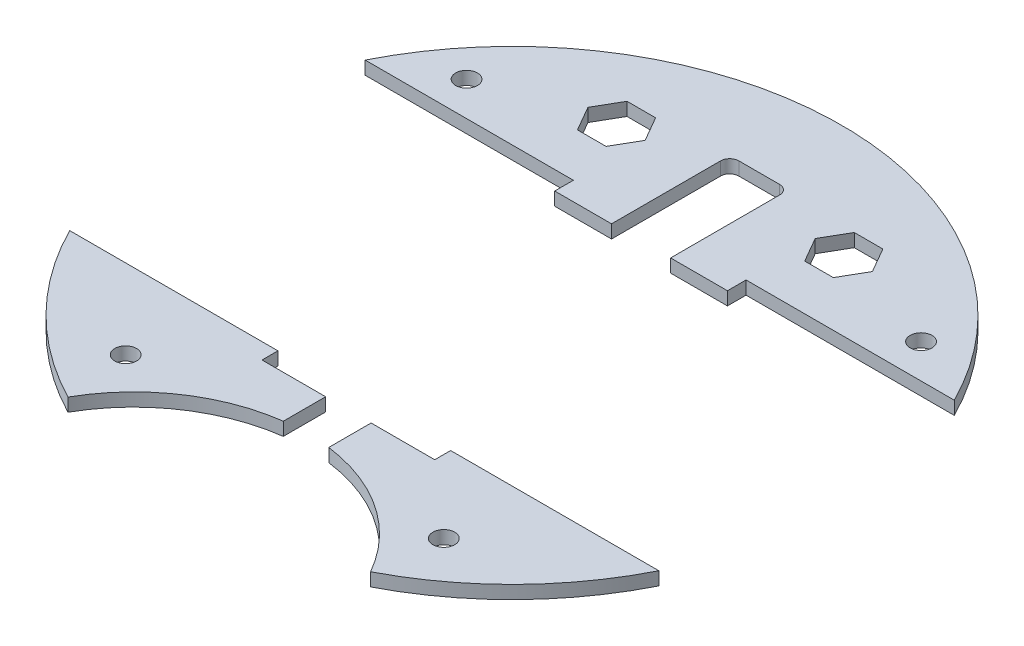
SolidWorks part; units mm, degrees
material "Acrylic (Medium-high impact)"
ref_plane "Front Plane" through (0, 0, 0) normal (0, 0, 1) x (1, 0, 0)
ref_plane "Top Plane" through (0, 0, 0) normal (0, 1, 0) x (1, 0, 0)
ref_plane "Right Plane" through (0, 0, 0) normal (1, 0, 0) x (0, 0, -1)
sketch "Sketch1" plane through (0, 0, 0) normal (0, 1, 0) x (1, 0, 0)
  line L0 (0, -83.2398) -> (-33.2911, -64.4046) construction
  line L1 (0, -83.2398) -> (0, 0) construction
  arc A0 (33.2911, -64.4046) -> (-33.2911, -64.4046) centre (0, 0) ccw
  arc A1 (33.2911, -64.4046) -> (-33.2911, -64.4046) centre (0, -83.2398) ccw
  dimension "D1" = 145
  dimension "D2" = 76.5
  dimension "D3" = 60.5
extrude "Boss-Extrude1" add sketch "Sketch1" along normal blind 2.9
sketch "solenoid placement" plane through (0, 2.9, 0) normal (0, 1, 0) x (1, 0, 0)
  line L4 (-19, -36) -> (19, -36)
  line L5 (-19, 28.4) -> (-19, -36)
  line L6 (19, 28.4) -> (-19, 28.4)
  line L7 (19, -36) -> (19, 28.4)
  line L8 (-19, -36) -> (19, -36)
  line L9 (-19, 28.4) -> (-19, -36)
  line L10 (19, 28.4) -> (-19, 28.4)
  line L11 (19, -36) -> (19, 28.4)
  dimension "D1" = 0
extrude "Cut-Extrude1" cut sketch "solenoid placement" against normal through all
sketch "Sketch4" plane through (0, 2.9, 0) normal (0, 1, 0) x (1, 0, 0)
  line L6 (-6.5, 28.1) -> (6.5, 28.1)
  line L7 (6.5, 28.1) -> (6.5, 52.4)
  line L8 (4.5, 54.4) -> (-4.5, 54.4)
  line L9 (-6.5, 52.4) -> (-6.5, 28.1)
  line L10 (-6.5, 28.1) -> (6.5, 28.1)
  line L11 (6.5, 28.1) -> (6.5, 52.4)
  line L12 (4.5, 54.4) -> (-4.5, 54.4)
  line L13 (-6.5, 52.4) -> (-6.5, 28.1)
  arc A4 (6.5, 52.4) -> (4.5, 54.4) centre (4.5, 52.4) ccw
  arc A5 (6.5, 52.4) -> (4.5, 54.4) centre (4.5, 52.4) ccw
  arc A6 (-4.5, 54.4) -> (-6.5, 52.4) centre (-4.5, 52.4) ccw
  arc A7 (-4.5, 54.4) -> (-6.5, 52.4) centre (-4.5, 52.4) ccw
  dimension "D1" = 0
extrude "Cut-Extrude4" cut sketch "Sketch4" against normal through all
sketch "Sketch5" plane through (0, 2.9, 0) normal (0, 1, 0) x (1, 0, 0)
  line L0 (0, 0) -> (0, 72.5) construction
  line L1 (-18.7069, 48) -> (-21.8534, 53.45)
  line L2 (-21.8534, 53.45) -> (-28.1466, 53.45)
  line L3 (-28.1466, 53.45) -> (-31.2931, 48)
  line L4 (-31.2931, 48) -> (-28.1466, 42.55)
  line L5 (-28.1466, 42.55) -> (-21.8534, 42.55)
  line L6 (-21.8534, 42.55) -> (-18.7069, 48)
  line L7 (21.8534, 42.55) -> (18.7069, 48)
  line L8 (28.1466, 42.55) -> (21.8534, 42.55)
  line L9 (31.2931, 48) -> (28.1466, 42.55)
  line L10 (28.1466, 53.45) -> (31.2931, 48)
  line L11 (21.8534, 53.45) -> (28.1466, 53.45)
  line L12 (18.7069, 48) -> (21.8534, 53.45)
  circle A0 centre (-25, 48) radius 5.45 construction
  circle A2 centre (25, 48) radius 5.45 construction
  arc A3 (33.2911, -64.4046) -> (-33.2911, -64.4046) centre (0, 0) ccw construction
  dimension "D3" = 10.9
extrude "Cut-Extrude5" cut sketch "Sketch5" against normal through all
sketch "Sketch6" plane through (0, 2.9, 0) normal (0, 1, 0) x (1, 0, 0)
  circle A1 centre (35, -50) radius 2.4
  circle A2 centre (35, -50) radius 2.4
  circle A3 centre (-35, -50) radius 2.4
  circle A4 centre (-35, -50) radius 2.4
  circle A5 centre (-50, 40) radius 2.4
  circle A6 centre (-50, 40) radius 2.4
  circle A7 centre (50, 40) radius 2.4
  circle A8 centre (50, 40) radius 2.4
  dimension "D1" = 0
  dimension "D2" = 0
  dimension "D3" = 0
  dimension "D4" = 0
extrude "Cut-Extrude6" cut sketch "Sketch6" against normal through all
sketch "Sketch3" plane through (0, 2.9, 0) normal (0, 1, 0) x (1, 0, 0)
  line L0 (-19, 28.4) -> (19, 28.4)
  line L1 (-72.5, -32.5) -> (72.5, -32.5)
  line L2 (-72.5, -32.5) -> (-72.5, 32.5)
  line L3 (-72.5, 32.5) -> (-19, 32.5)
  line L4 (72.5, -32.5) -> (72.5, 32.5)
  line L5 (-72.5, -32.5) -> (72.5, 32.5) construction
  line L6 (-72.5, 32.5) -> (72.5, -32.5) construction
  line L7 (19, 28.4) -> (19, 32.5)
  line L8 (-19, 28.4) -> (-19, 32.5)
  line L9 (19, 32.5) -> (72.5, 32.5)
  arc A0 (33.2911, -64.4046) -> (-33.2911, -64.4046) centre (0, 0) ccw construction
  point P0 (0, 0)
  dimension "D1" = 65
extrude "Cut-Extrude3" cut sketch "Sketch3" against normal through all
sketch "Sketch7" plane through (0, 2.9, 0) normal (0, 1, 0) x (1, 0, 0)
  line L4 (5, 0) -> (-5, 0)
  line L5 (5, -62.8025) -> (5, 0)
  line L6 (-5, -62.8025) -> (5, -62.8025)
  line L7 (-5, 0) -> (-5, -62.8025)
  line L8 (5, 0) -> (-5, 0)
  line L9 (5, -62.8025) -> (5, 0)
  line L10 (-5, -62.8025) -> (5, -62.8025)
  line L11 (-5, 0) -> (-5, -62.8025)
  dimension "D1" = 0
extrude "Cut-Extrude7" cut sketch "Sketch7" against normal through all
equation "\"smallPulleyTeeth\"= 15"
equation "\"largePulleyTeeth\"= 30"
equation "\"eighthThick\"= 2.9mm"
equation "\"sixteenthThick\" = 1.7mm"
equation "\"quarterThick\"=6.0mm"
equation "\"OD\" = 145mm"
equation "\"puckAngle\" = 60.5deg"
equation "\"D1@Sketch1\"=\"OD\""
equation "\"puckDiam\" = 76.5mm"
equation "\"D2@Sketch1\"=\"puckDiam\""
equation "\"D3@Sketch1\"=\"puckAngle\""
equation "\"D1@Boss-Extrude1\"=\"eighthThick\""
equation "\"axlePress\" = 5.9mm"
equation "\"press\" = 0.2mm"
equation "\"wheelClear\" = 0.3mm"
equation "\"10-32clear\" = 4.8mm"
equation "\"6-32clear\" = 3.3mm"
equation "\"8-32clear\" = 4.0mm"
equation "\"wheelHeight\" = 22mm"
equation "\"wheelWell\" = 65mm"
equation "\"D1@Sketch3\"=\"wheelWell\""
